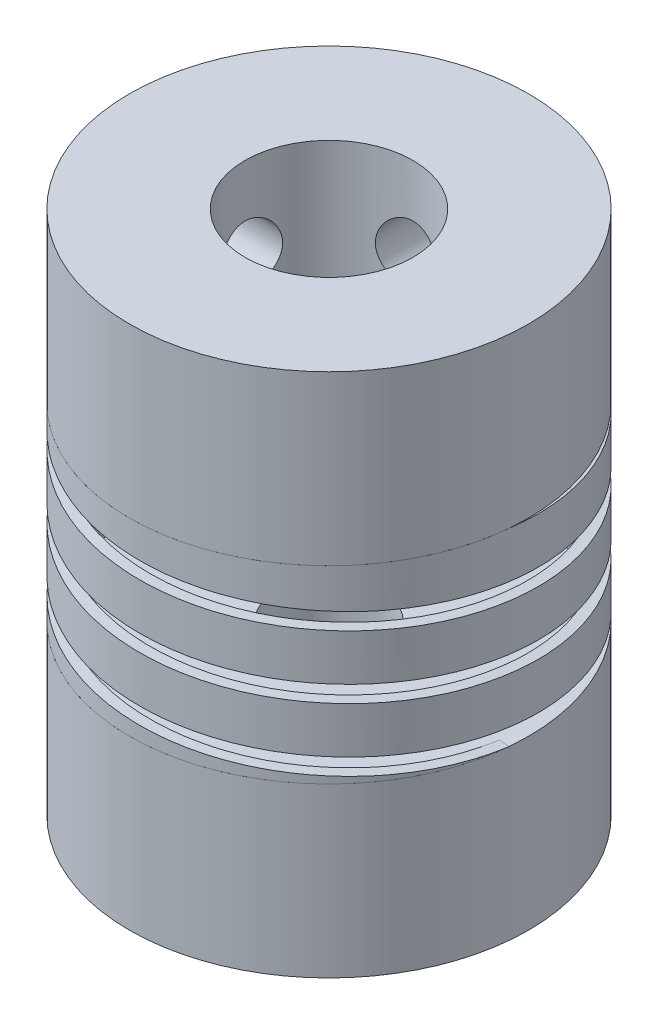
SolidWorks part; units mm, degrees
ref_plane "前视基准面" through (0, 0, 0) normal (0, 0, 1) x (1, 0, 0)
ref_plane "上视基准面" through (0, 0, 0) normal (0, 1, 0) x (1, 0, 0)
ref_plane "右视基准面" through (0, 0, 0) normal (1, 0, 0) x (0, 0, -1)
sketch "草图3" plane through (0, 0, 0) normal (0, 1, 0) x (1, 0, 0)
  circle A0 centre (0, 0) radius 9.5
extrude "凸台-拉伸8" add sketch "草图3" along normal blind 8
sketch "草图6" plane through (0, 0, 0) normal (0, -1, 0) x (1, 0, 0)
  circle A0 centre (0, 0) radius 2.5
extrude "切除-拉伸1" cut sketch "草图6" against normal blind 8
sketch "草图7" plane through (0, 0, 0) normal (1, 0, 0) x (0, 0, -1)
  circle A0 centre (0, 4) radius 1.5
extrude "切除-拉伸2" cut sketch "草图7" against normal blind 10
pattern_circular "阵列(圆周)2" count 2 every 90 about axis through (0, 8, 0) along (0, -1, 0) of "切除-拉伸2"
ref_plane "基准面5" through (0, 8, 0) normal (0, 1, 0) x (1, 0, 0)
sketch "草图8" plane through (0, 8, 0) normal (0, 1, 0) x (1, 0, 0)
  circle A0 centre (0, 0) radius 9.5
extrude "凸台-拉伸9" add sketch "草图8" along normal blind 9 separate body
ref_plane "基准面6" through (0, 17, 0) normal (0, 1, 0) x (1, 0, 0)
sketch "草图9" plane through (0, 17, 0) normal (0, 1, 0) x (1, 0, 0)
  circle A0 centre (0, 0) radius 9.5
extrude "凸台-拉伸10" add sketch "草图9" along normal blind 8 separate body
sketch "草图10" plane through (0, 25, 0) normal (0, 1, 0) x (1, 0, 0)
  circle A0 centre (0, 0) radius 4
extrude "切除-拉伸3" cut sketch "草图10" against normal blind 8
sketch "草图11" plane through (0, 0, 0) normal (1, 0, 0) x (0, 0, -1)
  line L0 (0, 25) -> (0, 21)
  line L1 (4, 25) -> (-4, 25) construction
  circle A0 centre (0, 21) radius 1.5
extrude "切除-拉伸4" cut sketch "草图11" against normal blind 10 contours A0 region at (0, 19.9693, 1.0307)
pattern_circular "阵列(圆周)3" count 2 every 90 about axis through (0, 25, 0) along (0, -1, 0) of "切除-拉伸4"
sketch "草图12" plane through (0, 17, 0) normal (0, 1, 0) x (1, 0, 0)
  circle A0 centre (0, 0) radius 9.5
curve "螺旋线/涡状线1" pitch 3 height 9 radius 9.5 left hand yes centre (0, 17, 0) axis (0, -1, 0) start towards (0, 0, -1)
sketch "草图14" plane through (0, 0, 0) normal (1, 0, 0) x (0, 0, -1)
  line L1 (9.5, 17) -> (8.995, 17)
  line L2 (9.5, 17) -> (9.5, 16.2048)
  line L3 (9.5, 16.2048) -> (8.995, 16.2048)
  line L4 (8.995, 17) -> (8.995, 16.2048)
sweep "切除-扫描1" cut profiles "草图14" path "螺旋线/涡状线1" align with end faces yes
sketch "草图15" plane through (0, 17, 0) normal (0, 1, 0) x (1, 0, 0)
  circle A0 centre (0, 0) radius 8.995
extrude "切除-拉伸5" cut sketch "草图15" against normal blind 10
